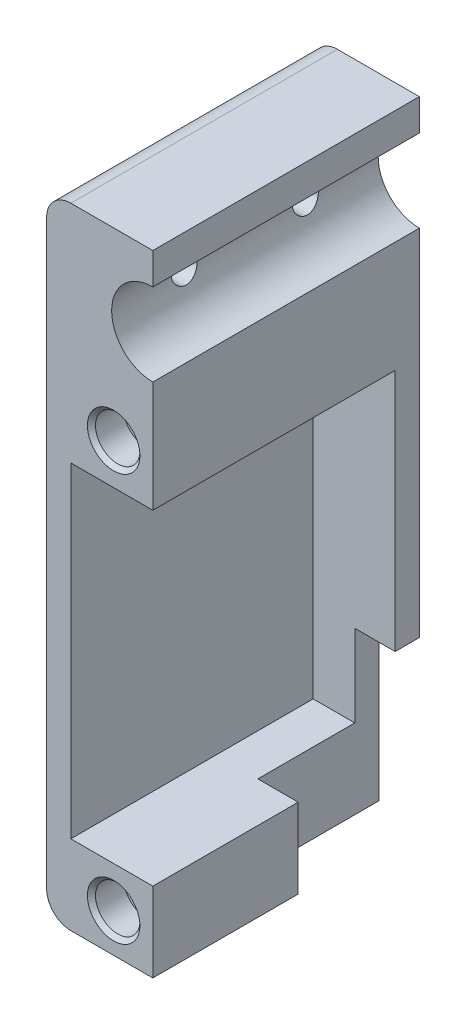
SolidWorks part; units mm, degrees
note: The reader was unsure of these and kept them because the rebuilt part matched: shared geometry of "Sketch1<2>".
ref_plane "Front Plane" through (0, 0, 0) normal (0, 0, 1) x (1, 0, 0)
ref_plane "Top Plane" through (0, 0, 0) normal (0, 1, 0) x (1, 0, 0)
ref_plane "Right Plane" through (0, 0, 0) normal (1, 0, 0) x (0, 0, -1)
sketch "Sketch1" plane through (0, 0, 0) normal (0, 0, 1) x (1, 0, 0)
  line L1 (-10.15, 20.15) -> (10.15, 20.15)
  line L2 (-10.15, 20.15) -> (-10.15, -20.15)
  line L3 (-10.15, -20.15) -> (10.15, -20.15)
  line L4 (10.15, 20.15) -> (10.15, -20.15)
  line L5 (-10.15, 20.15) -> (10.15, -20.15) construction
  line L6 (-10.15, -20.15) -> (10.15, 20.15) construction
  line L11 (-13.15, 30) -> (13.15, 30)
  line L12 (-13.15, 30) -> (-13.15, -30)
  line L13 (-13.15, -30) -> (13.15, -30)
  line L14 (13.15, 30) -> (13.15, -30)
  point P0 (0, 0)
  point P6 (0, 0)
  dimension "D1" = 40.3
  dimension "D2" = 20.3
  dimension "D3" = 3
  dimension "D4" = 60
extrude "Boss-Extrude1" add sketch "Sketch1" against normal blind 30
extrude "Boss-Extrude2" add sketch "Sketch1<2>" against normal blind 3 from surface at -30 starting at face at (0, 0, -30)
sketch "Sketch1<2>" plane through (0, 0, 0) normal (0, 0, 1) x (1, 0, 0) same geometry as "Sketch1"
sketch "Sketch2" plane through (0, 0, 0) normal (0, 0, 1) x (1, 0, 0)
  line L1 (-13.15, 30) -> (13.15, 30)
  line L2 (-13.15, 30) -> (-13.15, 48)
  line L3 (-13.15, 48) -> (13.15, 48)
  line L4 (13.15, 30) -> (13.15, 48)
  circle A0 centre (0, 39) radius 5.1
  point P8 (13.15, 39)
  dimension "D2" = 10.2
  dimension "D1" = 18
extrude "Boss-Extrude3" add sketch "Sketch2" against normal blind 33
sketch "Sketch3" plane through (0, -30, 0) normal (0, -1, 0) x (1, 0, 0)
  line L0 (-13.15, -33) -> (13.15, -33) construction
  line L1 (-5, -33) -> (5, -33)
  line L2 (-5, -33) -> (-5, -18)
  line L3 (-5, -18) -> (5, -18)
  line L4 (5, -33) -> (5, -18)
  line L6 (-13.15, -33) -> (-13.15, 0) construction
  dimension "D1" = 10
  dimension "D2" = 15
  dimension "D3" = 8.15
extrude "Cut-Extrude1" cut sketch "Sketch3" against normal blind 20
sketch "Sketch4" plane through (13.15, 0, 0) normal (1, 0, 0) x (0, 0, -1)
  line L0 (0, 39) -> (33, 39) construction
  line L1 (0, -30) -> (0, 48) construction
  line L2 (33, 48) -> (33, -30) construction
  line L3 (33, 48) -> (0, 48) construction
  line L5 (0, 33.9) -> (33, 33.9)
  line L6 (0, 33.9) -> (0, 44.1)
  line L7 (0, 44.1) -> (33, 44.1)
  line L8 (33, 33.9) -> (33, 44.1)
  circle A0 centre (9, 39) radius 1.6
  circle A1 centre (24, 39) radius 1.6
  dimension "D4" = 3.2
  dimension "D5" = 3.2
  dimension "D1" = 9
  dimension "D2" = 5.1
  dimension "D3" = 5.1
  dimension "D6" = 15
  dimension "D7" = 9
extrude "Cut-Extrude2" cut sketch "Sketch4" against normal through all contours A0 L0 | L0 A0 | A1 L0 | L0 A1
fillet "Fillet1" radius 3 4 edges at (-13.15, 48, -16.5) (13.15, 48, -16.5) (-13.15, -30, -16.5) (13.15, -30, -16.5)
sketch "Sketch5" plane through (0, 0, 0) normal (0, 0, 1) x (1, 0, 0)
  circle A0 centre (5.15, 25.2) radius 2.75
  circle A1 centre (-4.85, 25.2) radius 2.75
  circle A2 centre (5.15, -25.2) radius 2.75
  circle A3 centre (-4.85, -25.2) radius 2.75
  dimension "D1" = 5.5
  dimension "D2" = 5.5
  dimension "D3" = 5.5
  dimension "D4" = 5.5
extrude "Cut-Extrude3" cut sketch "Sketch5" against normal blind 4 contours A0 | A1 | A2 | A3
chamfer "Chamfer1" distance 0.5 angle 45 4 edges at (-2.1, 25.2, 0) (7.9, 25.2, 0) (-2.1, -25.2, 0) (7.9, -25.2, 0)
ref_plane "Plane1" through (0, 0, 0) normal (-1, 0, 0) x (0, 0, 1)
other "SurfaceCut2"
